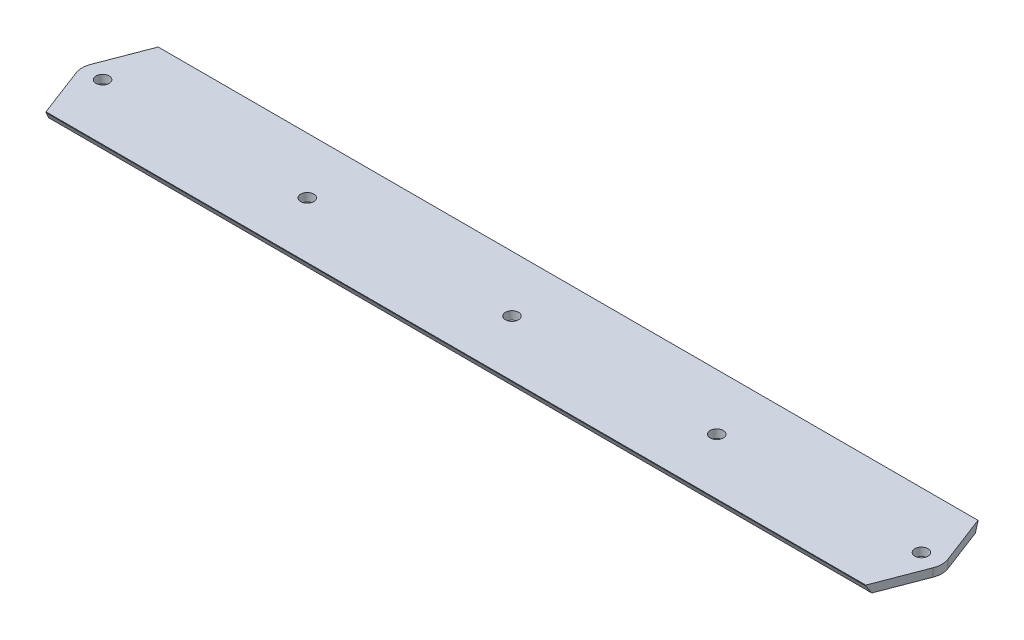
SolidWorks part; units mm, degrees
material "Медь"
ref_plane "Front" through (0, 0, 0) normal (0, 0, 1) x (1, 0, 0)
ref_plane "Top" through (0, 0, 0) normal (0, 1, 0) x (1, 0, 0)
ref_plane "Right" through (0, 0, 0) normal (1, 0, 0) x (0, 0, -1)
sketch "Эскиз1" plane through (0, 0, 0) normal (0, 1, 0) x (1, 0, 0)
  line L0 (-125, 14) -> (75, 14)
  line L1 (75, -14) -> (-75, -14)
  line L2 (75, 14) -> (-125, -14) construction
  line L3 (-125, 14) -> (75, -14) construction
  line L4 (-129.6702, 1.7857) -> (-125, 14)
  line L5 (-125, 14) -> (-125, 1.6)
  line L9 (0, 0) -> (0, 14) construction
  line L10 (75, -14) -> (79.6702, -1.7857)
  line L11 (75, 14) -> (79.6702, 1.7857)
  line L14 (-129.6702, -1.7857) -> (-125, -14)
  line L15 (-125, -14) -> (-75, -14)
  circle A0 centre (-75, 0) radius 1.6
  circle A2 centre (75, 0) radius 1.6
  arc A3 (79.6702, 1.7857) -> (79.6702, -1.7857) centre (75, 0) cw
  circle A4 centre (-25, 0) radius 1.6
  circle A5 centre (25, 0) radius 1.6
  circle A7 centre (-125, 0) radius 1.6
  arc A8 (-129.6702, 1.7857) -> (-129.6702, -1.7857) centre (-125, 0) ccw
  point P0 (0, 0)
  dimension "D3" = 3.2
  dimension "D4" = 5
  dimension "D6" = 50
  dimension "D2" = 3.2
  dimension "D1" = 200
  dimension "D7" = 50
  dimension "D5" = 3
extrude "Бобышка-Вытянуть1" add sketch "Эскиз1" along normal blind 2 contours A2 A0 L1 A5 A4 | A3 L11 A2 L10 | A0 region at (-25, 0, -11.8814)
sketch "Эскиз2" plane through (0, 2, 0) normal (0, 1, 0) x (1, 0, 0)
  line L0 (-125, 14) -> (-125, 1.6)
  circle A0 centre (-125, 0) radius 1.6 construction
ref_plane "Плоскость1" through (-125, 0, 0) normal (-1, 0, 0) x (0, 0, 1)
sketch "Эскиз4" plane through (-125, 0, 0) normal (-1, 0, 0) x (0, 0, 1)
  line L0 (-14, 2) -> (-13.8, 2)
  line L1 (-14, 2) -> (-1.6, 2) construction
  line L2 (-13.8, 2) -> (-12.6453, 0)
  line L3 (-1.7857, 0) -> (-14, 0) construction
  line L4 (-14, 2) -> (-14, 0)
  line L5 (-14, 0) -> (-12.6453, 0)
  line L6 (0, 2) -> (0, 0)
  line L7 (1.7857, 2) -> (-1.7857, 2) construction
  line L8 (14, 0) -> (12.6453, 0)
  line L9 (14, 2) -> (14, 0)
  line L10 (14, 2) -> (13.8, 2)
  line L11 (13.8, 2) -> (12.6453, 0)
  dimension "D1" = 120
  dimension "D2" = 0.2
extrude "Вырез-Вытянуть1" cut sketch "Эскиз4" against normal blind 210 and the other way blind 5 contours L4 L5 L2 L0 | L9 L8 L11 L10 region at (-125, 0.7524, -13.5399)
chamfer "Фаска2" distance 0.2 angle 30 2 edges at (-25, 2, 13.8) (-25, 2, -13.8) first distance on face at (-25, 1, 13.2226) first distance on face at (-25, 1, -13.2226)
